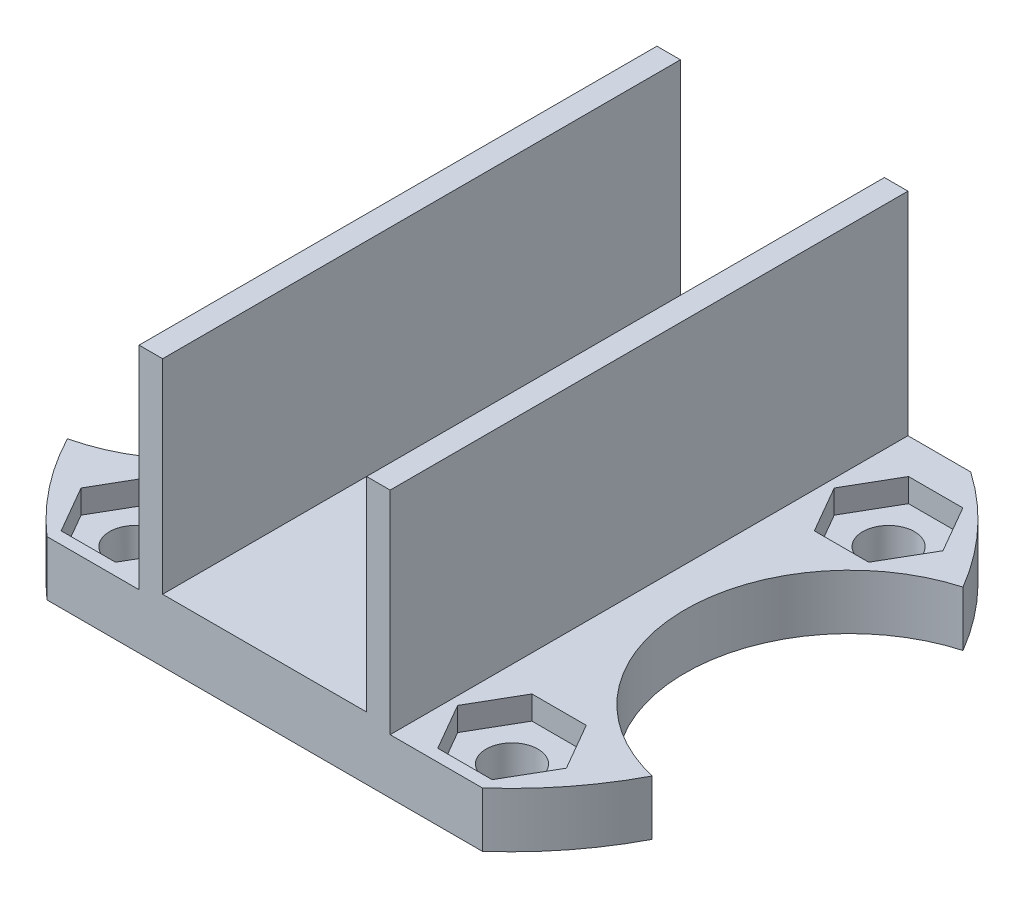
SolidWorks part; units mm, degrees
ref_plane "Front Plane" through (0, 0, 0) normal (0, 0, 1) x (1, 0, 0)
ref_plane "Top Plane" through (0, 0, 0) normal (0, 1, 0) x (1, 0, 0)
ref_plane "Right Plane" through (0, 0, 0) normal (1, 0, 0) x (0, 0, -1)
sketch "Sketch1" plane through (0, 0, 0) normal (0, 1, 0) x (1, 0, 0)
  line L0 (-23.7557, 20.1202) -> (0.2443, -3.8798) construction
  line L1 (0.2443, 20.1202) -> (-23.7557, -3.8798) construction
  circle A0 centre (-23.7557, 20.1202) radius 1.65
  circle A1 centre (0.2443, 20.1202) radius 1.65
  circle A2 centre (-23.7557, -3.8798) radius 1.65
  circle A3 centre (0.2443, -3.8798) radius 1.65
  circle A4 centre (-11.7557, 8.1202) radius 21
  point P4 (-11.7557, 8.1202)
  dimension "D1" = 3.3
  dimension "D2" = 24
  dimension "D7" = 42
  dimension "D3" = 24
  dimension "D4" = 24
  dimension "D5" = 24
  dimension "D6" = 24
extrude "Boss-Extrude2" add sketch "Sketch1" along normal blind 3.5
ref_axis "Axis1" through (-11.7557, 3.5, -8.1202) along (0, -1, 0)
sketch "Sketch3" plane through (0, 3.5, 0) normal (0, 1, 0) x (1, 0, 0)
  line L0 (-23.7557, 25.3539) -> (0.2443, 25.3539)
  circle A0 centre (-11.7557, 8.1202) radius 21 construction
  dimension "D1" = 24
extrude "Cut-Extrude1" cut sketch "Sketch3" against normal through all and the other way through all
sketch "Sketch4" plane through (0, 0, -25.3539) normal (0, 0, -1) x (-1, 0, 0)
  line L0 (-0.2443, 3.5) -> (-0.2443, 0) construction
  line L1 (3.7557, 13.2251) -> (3.7557, 3.5)
  line L2 (-0.2443, 3.5) -> (23.7557, 3.5) construction
  line L3 (19.7557, 13.2251) -> (19.7557, 3.5)
  line L4 (19.7557, 3.5) -> (3.7557, 3.5)
  line L5 (19.7557, 13.2251) -> (19.7557, 17)
  line L6 (23.7557, 0) -> (23.7557, 3.5) construction
  line L7 (18.2557, 17) -> (18.2557, 4)
  line L8 (18.2557, 4) -> (5.2557, 4)
  line L9 (5.2557, 17) -> (5.2557, 4)
  line L10 (18.2557, 17) -> (5.2557, 4) construction
  line L11 (18.2557, 4) -> (5.2557, 17) construction
  line L12 (5.2557, 17) -> (3.7557, 17)
  line L13 (3.7557, 17) -> (3.7557, 13.2251)
  line L15 (19.7557, 17) -> (18.2557, 17)
  point P14 (-0.2443, 1.75)
  dimension "D1" = 0.5
  dimension "D2" = 4
  dimension "D3" = 1.5
  dimension "D4" = 13
  dimension "D5" = 1.5
  dimension "D6" = 13
  dimension "D7" = 4
extrude "Boss-Extrude3" add sketch "Sketch4" against normal blind 33
sketch "Sketch6" plane through (0, 0, 0) normal (0, -1, 0) x (1, 0, 0)
  line L1 (-22.0236, -17.1202) -> (-25.4877, -17.1202)
  line L2 (-25.4877, -17.1202) -> (-27.2198, -20.1202)
  line L3 (-27.2198, -20.1202) -> (-25.4877, -23.1202)
  line L4 (-25.4877, -23.1202) -> (-22.0236, -23.1202)
  line L5 (-22.0236, -23.1202) -> (-20.2916, -20.1202)
  line L6 (-20.2916, -20.1202) -> (-22.0236, -17.1202)
  line L7 (-22.0236, 0.8798) -> (-20.2916, 3.8798)
  line L8 (-20.2916, 3.8798) -> (-22.0236, 6.8798)
  line L9 (-22.0236, 6.8798) -> (-25.4877, 6.8798)
  line L10 (-25.4877, 6.8798) -> (-27.2198, 3.8798)
  line L11 (-27.2198, 3.8798) -> (-25.4877, 0.8798)
  line L12 (-25.4877, 0.8798) -> (-22.0236, 0.8798)
  line L13 (1.9764, 0.8798) -> (3.7084, 3.8798)
  line L14 (3.7084, 3.8798) -> (1.9764, 6.8798)
  line L15 (1.9764, 6.8798) -> (-1.4877, 6.8798)
  line L16 (-1.4877, 6.8798) -> (-3.2198, 3.8798)
  line L17 (-3.2198, 3.8798) -> (-1.4877, 0.8798)
  line L18 (-1.4877, 0.8798) -> (1.9764, 0.8798)
  line L19 (1.9764, -17.1202) -> (-1.4877, -17.1202)
  line L20 (-1.4877, -17.1202) -> (-3.2198, -20.1202)
  line L21 (-3.2198, -20.1202) -> (-1.4877, -23.1202)
  line L22 (-1.4877, -23.1202) -> (1.9764, -23.1202)
  line L23 (1.9764, -23.1202) -> (3.7084, -20.1202)
  line L24 (3.7084, -20.1202) -> (1.9764, -17.1202)
  circle A0 centre (-23.7557, -20.1202) radius 3 construction
  circle A1 centre (-23.7557, 3.8798) radius 3 construction
  circle A2 centre (0.2443, 3.8798) radius 3 construction
  circle A3 centre (0.2443, -20.1202) radius 3 construction
  dimension "D1" = 6
  dimension "D2" = 6
  dimension "D3" = 6
  dimension "D4" = 6
extrude "Cut-Extrude2" cut sketch "Sketch6" along normal blind 1.5 from offset 3.5 offset against normal yes
sketch "Sketch7" plane through (0, 0, 0) normal (0, -1, 0) x (1, 0, 0)
  line L0 (-18.2557, -25.3539) -> (-5.2557, -25.3539) construction
  line L1 (9.2374, 16.7164) -> (-32.7494, 16.7164)
  line L2 (9.2374, 16.7164) -> (9.2374, 7.6461)
  line L3 (9.2374, 7.6461) -> (-32.7494, 7.6461)
  line L4 (-32.7494, 16.7164) -> (-32.7494, 7.6461)
  circle A0 centre (-32.7494, -8.6322) radius 10.5
  arc A1 (0.2443, -25.3539) -> (-23.7557, -25.3539) centre (-11.7557, -8.1202) ccw construction
  circle A2 centre (9.2374, -8.6585) radius 10.5
  point P13 (-11.7557, -25.3539)
  dimension "D1" = 21
  dimension "D2" = 21
  dimension "D3" = 33
extrude "Cut-Extrude3" cut sketch "Sketch7" against normal through all
